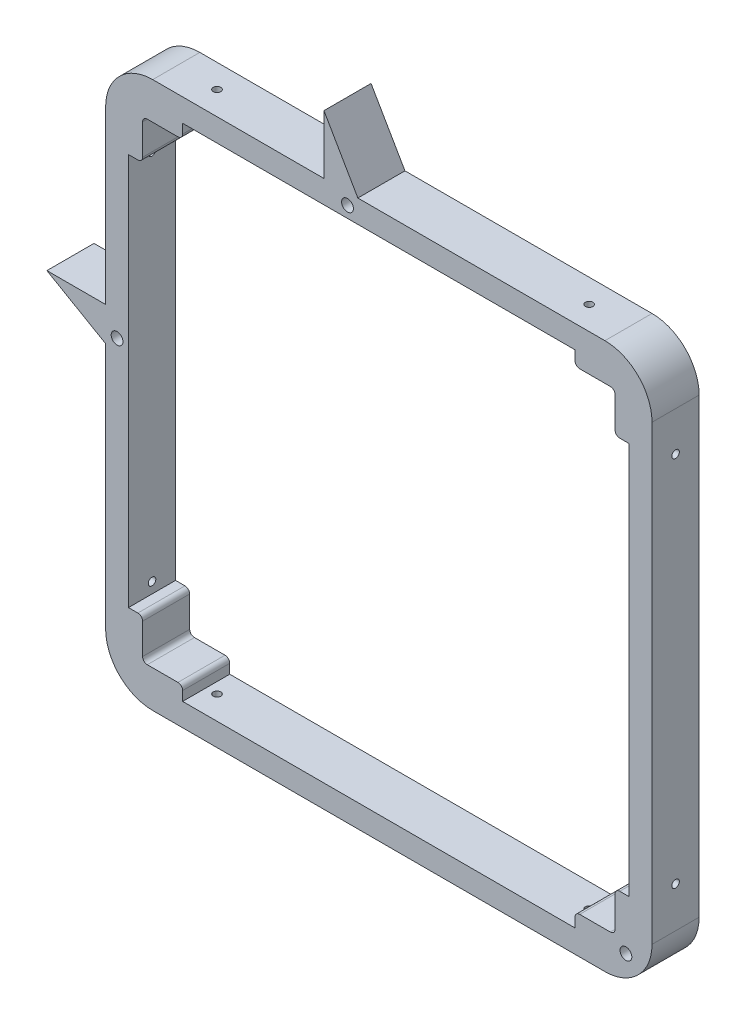
SolidWorks part; units mm, degrees
material "Nylon 101"
ref_plane "Front Plane" through (0, 0, 0) normal (0, 0, 1) x (1, 0, 0)
ref_plane "Top Plane" through (0, 0, 0) normal (0, 1, 0) x (1, 0, 0)
ref_plane "Right Plane" through (0, 0, 0) normal (1, 0, 0) x (0, 0, -1)
sketch "Sketch1" plane through (0, 0, 0) normal (0, 0, 1) x (1, 0, 0)
  line L13 (50.0019, -50.0019) -> (58, -58) construction
  line L14 (53, -41.5) -> (50.0019, -41.5)
  line L17 (41.5, -53) -> (41.5, -50.0019)
  line L18 (50.0019, -44.9586) -> (53, -44.9586)
  line L20 (53, -44.9586) -> (53, -53)
  line L23 (53, -53) -> (44.9586, -53)
  line L24 (44.9586, -53) -> (44.9586, -50.0019)
  line L25 (50.0019, -41.5) -> (50.0019, -50.0019)
  line L27 (50.0019, -50.0019) -> (41.5, -50.0019)
  line L35 (-41.5, 53) -> (41.5, 53)
  line L37 (50.0019, -50.0019) -> (50.0019, -41.5)
  line L38 (41.5, -50.0019) -> (50.0019, -50.0019)
  line L39 (53, -44.9586) -> (50.0019, -44.9586)
  line L40 (53, -53) -> (53, -44.9586)
  line L42 (44.9586, -53) -> (53, -53)
  line L43 (44.9586, -50.0019) -> (44.9586, -53)
  line L44 (53, -41.5) -> (50.0019, -41.5)
  line L45 (41.5, -53) -> (41.5, -50.0019)
  line L47 (53, -41.5) -> (53, 41.5)
  line L50 (41.5, -53) -> (-41.5, -53)
  line L52 (-41.5, -53) -> (-41.5, -50.0019)
  line L53 (-53, -41.5) -> (-50.0019, -41.5)
  line L54 (-44.96, -50.0019) -> (-44.96, -53)
  line L55 (-44.96, -53) -> (-53, -53)
  line L57 (-53, -53) -> (-53, -44.96)
  line L58 (-53, -44.96) -> (-50.0019, -44.96)
  line L59 (-41.5, -50.0019) -> (-50.0019, -50.0019)
  line L60 (-50.0019, -50.0019) -> (-50.0019, -41.5)
  line L61 (-53, -41.5) -> (-53, 41.5)
  line L63 (58, 58) -> (58, -58)
  line L65 (-50.0019, -50.0019) -> (-41.5, -50.0019)
  line L66 (-50.0019, -41.5) -> (-50.0019, -50.0019)
  line L67 (-44.96, -53) -> (-44.96, -50.0019)
  line L68 (-53, -53) -> (-44.96, -53)
  line L70 (-53, -44.96) -> (-53, -53)
  line L71 (-50.0019, -44.96) -> (-53, -44.96)
  line L72 (-41.5, -53) -> (-41.5, -50.0019)
  line L73 (-53, -41.5) -> (-50.0019, -41.5)
  line L75 (58, -58) -> (-58, -58)
  line L77 (-50.0019, -50.0019) -> (-58, -58) construction
  line L79 (-58, -58) -> (-58, 58)
  line L81 (-53, 41.5) -> (-50.0019, 41.5)
  line L82 (-41.5, 53) -> (-41.5, 50.0019)
  line L83 (-50.0019, 44.96) -> (-53, 44.96)
  line L84 (-53, 44.96) -> (-53, 53)
  line L86 (-53, 53) -> (-44.96, 53)
  line L87 (-44.96, 53) -> (-44.96, 50.0019)
  line L88 (-50.0019, 41.5) -> (-50.0019, 50.0019)
  line L89 (-50.0019, 50.0019) -> (-41.5, 50.0019)
  line L90 (-58, 58) -> (58, 58)
  line L94 (-50.0019, 50.0019) -> (-50.0019, 41.5)
  line L95 (-41.5, 50.0019) -> (-50.0019, 50.0019)
  line L96 (-53, 44.96) -> (-50.0019, 44.96)
  line L97 (-53, 53) -> (-53, 44.96)
  line L99 (-44.96, 53) -> (-53, 53)
  line L100 (-44.96, 50.0019) -> (-44.96, 53)
  line L101 (-53, 41.5) -> (-50.0019, 41.5)
  line L102 (-41.5, 53) -> (-41.5, 50.0019)
  line L106 (-50.0019, 50.0019) -> (-58, 58) construction
  line L110 (41.5, 53) -> (41.5, 50.0019)
  line L111 (53, 41.5) -> (50.0019, 41.5)
  line L112 (44.9586, 50.0019) -> (44.9586, 53)
  line L113 (44.9586, 53) -> (53, 53)
  line L115 (53, 53) -> (53, 44.96)
  line L116 (53, 44.96) -> (50.0019, 44.96)
  line L117 (41.5, 50.0019) -> (50.0019, 50.0019)
  line L118 (50.0019, 50.0019) -> (50.0019, 41.5)
  line L123 (50.0019, 50.0019) -> (41.5, 50.0019)
  line L124 (50.0019, 41.5) -> (50.0019, 50.0019)
  line L125 (44.9586, 53) -> (44.9586, 50.0019)
  line L126 (53, 53) -> (44.9586, 53)
  line L128 (53, 44.96) -> (53, 53)
  line L129 (50.0019, 44.96) -> (53, 44.96)
  line L130 (41.5, 53) -> (41.5, 50.0019)
  line L131 (53, 41.5) -> (50.0019, 41.5)
  line L135 (50.0019, 50.0019) -> (58, 58) construction
  point P2 (0, 58)
  point P4 (0, 53)
  point P6 (0, -53)
  point P7 (0, -58)
  point P10 (53, 0)
  point P11 (-53, 0)
  point P16 (-58, 0)
  point P17 (58, 0)
  dimension "D1" = 106
  dimension "D2" = 5
  dimension "D3" = 2.9981
extrude "base" add sketch "Sketch1" along normal mid plane 10 contours L20 L13 L14 L25 L18 | L13 L23 L24 L27 L17 | L13 L27 L24 L23 | L25 L13 L20 L18 | L117 L118 L116 L115 L113 L112 | L88 L89 L87 L86 L84 L83 | L59 L60 L58 L57 L55 L54 region at (51.5009, -45.0723, 0) region at (50.1156, 47.4809, 0) region at (-45.0737, -51.5009, 0) region at (-47.4809, 50.1156, 0) region at (56.3595, 0, 0)
ref_plane "Plane3" through (0, 0, 15) normal (0, 0, 1) x (1, 0, 0)
sketch "Sketch7" plane through (0, 0, 15) normal (0, 0, 1) x (1, 0, 0)
  line L0 (-41.65, 53.15) -> (41.65, 53.15)
  line L1 (41.65, 53.15) -> (41.65, 50.1519)
  line L2 (41.65, 50.1519) -> (50.1519, 50.1519)
  line L3 (50.1519, 50.1519) -> (50.1519, 41.65)
  line L4 (50.1519, 41.65) -> (53.15, 41.65)
  line L5 (53.15, 41.65) -> (53.15, -41.65)
  line L6 (53.15, -41.65) -> (50.1519, -41.65)
  line L7 (50.1519, -41.65) -> (50.1519, -50.1519)
  line L8 (50.1519, -50.1519) -> (41.65, -50.1519)
  line L9 (41.65, -50.1519) -> (41.65, -53.15)
  line L10 (41.65, -53.15) -> (-41.65, -53.15)
  line L11 (-41.65, -53.15) -> (-41.65, -50.1519)
  line L12 (-41.65, -50.1519) -> (-50.1519, -50.1519)
  line L13 (-50.1519, -50.1519) -> (-50.1519, -41.65)
  line L14 (-50.1519, -41.65) -> (-53.15, -41.65)
  line L15 (-53.15, -41.65) -> (-53.15, 41.65)
  line L16 (-53.15, 41.65) -> (-50.1519, 41.65)
  line L17 (-50.1519, 41.65) -> (-50.1519, 50.1519)
  line L18 (-50.1519, 50.1519) -> (-41.65, 50.1519)
  line L19 (-41.65, 50.1519) -> (-41.65, 53.15)
  line L21 (-41.5, 53) -> (41.5, 53) construction
  line L22 (-41.5, 53) -> (-41.5, 50.0019) construction
  line L23 (-50.0019, 50.0019) -> (-41.5, 50.0019) construction
  line L24 (-50.0019, 41.5) -> (-50.0019, 50.0019) construction
  line L25 (-53, 41.5) -> (-50.0019, 41.5) construction
  line L26 (-53, -41.5) -> (-53, 41.5) construction
  line L27 (-53, -41.5) -> (-50.0019, -41.5) construction
  line L28 (-50.0019, -50.0019) -> (-50.0019, -41.5) construction
  line L29 (-41.5, -50.0019) -> (-50.0019, -50.0019) construction
  line L30 (-41.5, -53) -> (-41.5, -50.0019) construction
  line L31 (41.5, -53) -> (-41.5, -53) construction
  line L32 (41.5, -53) -> (41.5, -50.0019) construction
  line L33 (50.0019, -41.5) -> (50.0019, -50.0019) construction
  line L34 (53, -41.5) -> (53, 41.5) construction
  line L35 (50.0019, 50.0019) -> (50.0019, 41.5) construction
  line L36 (53, 41.5) -> (50.0019, 41.5) construction
  line L37 (41.5, 50.0019) -> (50.0019, 50.0019) construction
  dimension "D1" = 0.15
  dimension "D2" = 0.15
  dimension "D3" = 0.15
  dimension "D4" = 0.15
  dimension "D5" = 0.15
  dimension "D6" = 0.15
  dimension "D7" = 0.15
  dimension "D8" = 0.15
  dimension "D9" = 0.15
  dimension "D10" = 0.15
  dimension "D11" = 0.15
  dimension "D12" = 0.15
  dimension "D13" = 0.15
  dimension "D14" = 0.15
  dimension "D15" = 0.15
  dimension "D16" = 0.15
  dimension "D17" = 0.15
ref_plane "arm plane" through (0, 0, 0) normal (0.7071, 0.7071, 0) x (0.7071, -0.7071, 0)
sketch "Sketch2" plane through (0, 0, 0) normal (0.7071, 0.7071, 0) x (0.7071, -0.7071, 0)
  line L4 (70.9255, 5) -> (82.0244, 5)
  line L8 (82.0244, 5) -> (82.0244, 44)
  line L9 (82.0244, 44) -> (32.0244, 44)
  line L12 (32.0244, 44) -> (32.0244, 33)
  line L13 (32.0244, 33) -> (70.9255, 33)
  line L14 (70.9255, 33) -> (70.9255, 5)
  dimension "D1" = 50
  dimension "D2" = 11
  dimension "D4" = 28
extrude "arm" add sketch "Sketch2" along normal mid plane 10
ref_plane "shim supports plane" through (0, 0, -5) normal (0, 0, -1) x (-1, 0, 0)
sketch "Sketch3" plane through (0, 0, 0) normal (0, 0, 1) x (1, 0, 0)
  line L1 (61.5355, -54.4645) -> (54.4645, -61.5355) construction
  line L6 (58, 58) -> (58, -50.9289) construction
  line L7 (50.9289, -58) -> (-58, -58) construction
  line L8 (19.1091, -26.1802) -> (46.6163, -53.6874) construction
  line L9 (58, -50.9289) -> (61.5355, -54.4645) construction
  line L10 (54.818, -61.8891) -> (61.8891, -54.818)
  line L11 (61.8891, -54.818) -> (58, -50.9289)
  line L12 (58, -50.9289) -> (58, -58)
  line L13 (58, -58) -> (50.9289, -58)
  line L14 (50.9289, -58) -> (54.818, -61.8891)
  dimension "D1" = 0.5
extrude "Cut-Extrude1" cut sketch "Sketch3" against normal through all
ref_plane "Plane2" through (0, 0, -5) normal (0, 0, -1) x (-1, 0, 0)
sketch "Sketch5" plane through (0, 0, -5) normal (0, 0, -1) x (-1, 0, 0)
  line L0 (-46.6163, -53.6874) -> (-43.0808, -50.1519)
  line L7 (-50.1519, -43.0808) -> (-53.6874, -46.6163)
  line L8 (-53.6874, -46.6163) -> (-53.6874, -53.6874)
  line L9 (-50.0019, -50.0019) -> (-58, -58) construction
  line L10 (-53.6874, -53.6874) -> (-46.6163, -53.6874)
  line L12 (-53.6874, -46.6163) -> (-58, -50.9289) construction
  line L14 (-50.1519, -41.65) -> (-50.1519, -50.1519) construction
  line L15 (-50.1519, -50.1519) -> (-41.65, -50.1519) construction
  line L16 (-50.1519, -43.0808) -> (-50.1519, -50.1519)
  line L17 (-50.1519, -50.1519) -> (-43.0808, -50.1519)
  dimension "D1" = 5
  dimension "D2" = 10
extrude "Boss-Extrude4" add sketch "Sketch5" along normal up to surface (28 mm away) contours L8 L10 L0 L7 | L7 L8 L10 L0 L17 L16 region at (50.1519, -53.5374, -5) up to face at (36.3983, -36.3983, -33)
extrude "clearance" cut sketch "Sketch7" against normal up to surface (20 mm away) up to face at (0, 0, -5)
sketch "Sketch10" plane through (0, 0, 0) normal (0, 1, 0) x (1, 0, 0)
  line L0 (41.65, 5) -> (41.65, -5) construction
  circle A0 centre (39.65, 0) radius 0.8
  circle A1 centre (-39.35, 0) radius 0.8
  point P5 (41.65, 0)
  dimension "D1" = 1.6
  dimension "D2" = 2
  dimension "D3" = 79
hole_wizard "M2x0.4 Tapped Hole1" positions "Sketch11" profile "Sketch12" tap size "M2x0.4" standard "ANSI Metric" end condition through all
sketch "Sketch11" plane through (0, 0, 0) normal (0, 1, 0) x (1, 0, 0)
  point P0 (-39.35, 0)
  point P2 (39.65, 0)
sketch "Sketch12" plane through (-39.35, 0, 0) normal (1, 0, 0) x (0, 0, -1)
  line L0 (0, 0) -> (0, 58)
  line L1 (0, 58) -> (0.8, 58)
  line L2 (0.8, 58) -> (0.8, 0)
  line L5 (0.8, 0) -> (0, 0)
  line L11 (0, -6.35) -> (0, 107.95) construction
  dimension "Thru Tap Drill Dia." = 1.6
  dimension "Thru Tap Drill Depth" = 58
cosmetic thread "Hole Thread1" parameters "D2"=2
cosmetic thread "Hole Thread2" parameters "D2"=2
mirror "Mirror1" about plane through (0, 0, 0) normal (0, 1, 0) of "M2x0.4 Tapped Hole1"
cosmetic thread "Hole Thread3" parameters "D2"=2
cosmetic thread "Hole Thread4" parameters "D2"=2
sketch "Sketch13" plane through (0, 0, 0) normal (1, 0, 0) x (0, 0, -1)
  line L2 (5, 41.65) -> (-5, 41.65) construction
  circle A0 centre (0, 39.65) radius 0.8
  circle A1 centre (0, -39.35) radius 0.8
  dimension "D1" = 1.6
  dimension "D3" = 79
  dimension "D2" = 2
hole_wizard "M2x0.4 Tapped Hole2" positions "Sketch14" profile "Sketch15" tap size "M2x0.4" standard "ANSI Metric" end condition through all
sketch "Sketch14" plane through (0, 0, 0) normal (1, 0, 0) x (0, 0, -1)
  point P0 (0, 39.65)
  point P3 (0, -39.35)
sketch "Sketch15" plane through (0, 39.65, 0) normal (0, 1, 0) x (0, 0, 1)
  line L0 (0, 0) -> (0, 58)
  line L1 (0, 58) -> (0.8, 58)
  line L2 (0.8, 58) -> (0.8, 0)
  line L5 (0.8, 0) -> (0, 0)
  line L11 (0, -6.35) -> (0, 107.95) construction
  dimension "Thru Tap Drill Dia." = 1.6
  dimension "Thru Tap Drill Depth" = 58
cosmetic thread "Hole Thread5" parameters "D2"=2
cosmetic thread "Hole Thread6" parameters "D2"=2
mirror "Mirror2" about plane through (0, 0, 0) normal (1, 0, 0) of "M2x0.4 Tapped Hole2"
cosmetic thread "Hole Thread7" parameters "D2"=2
cosmetic thread "Hole Thread8" parameters "D2"=2
sketch "Sketch16" plane through (0, 0, -5) normal (0, 0, -1) x (-1, 0, 0)
  line L0 (53.15, 11.65) -> (70.4705, 11.65)
  line L6 (53.15, -41.65) -> (53.15, 41.65) construction
  line L10 (-58, -58) -> (58, 58) construction
  line L18 (70.4705, 11.65) -> (53.15, 1.65)
  line L19 (53.15, 1.65) -> (53.15, 11.65)
  dimension "D1" = 20
  dimension "D2" = 10
  dimension "D3" = 30
extrude "extender" add sketch "Sketch16" along normal blind 29 contours L19 L18 region at (-58.9235, 8.3167, -5)
ref_plane "Plane5" through (0, 0, -34) normal (0, 0, -1) x (-1, 0, 0)
sketch "Sketch17" plane through (0, 0, -34) normal (0, 0, -1) x (-1, 0, 0)
  line L2 (106.183, 64.683) -> (114.8433, 56.0228)
  line L4 (53.15, 1.65) -> (53.15, 11.65)
  line L5 (53.15, 11.65) -> (106.183, 64.683)
  line L9 (-50.9289, -58) -> (-19.1091, -26.1802) construction
  line L14 (114.8433, 56.0228) -> (70.4705, 11.65)
  line L15 (70.4705, 11.65) -> (53.15, 1.65)
  dimension "D2" = 75
extrude "angled horizontal" add sketch "Sketch17" along normal blind 10
sketch "Sketch21" plane through (0, 0, 0) normal (0, 0, 1) x (1, 0, 0)
  line L0 (-53.15, 1.65) -> (-53.15, 11.65)
  line L1 (-70.4705, 11.65) -> (-53.15, 11.65)
  line L2 (-70.4705, 11.65) -> (-53.15, 1.65)
  line L6 (-70.4705, 11.65) -> (-58, 4.4501) construction
  line L8 (3.8891, -3.8891) -> (-3.8891, 3.8891) construction
  line L9 (-11.65, 70.4705) -> (-1.65, 53.15)
  line L10 (-11.65, 70.4705) -> (-11.65, 53.15)
  line L11 (-1.65, 53.15) -> (-11.65, 53.15)
  line L12 (-53.15, 38.85) -> (-53.15, 40.45) construction
  line L14 (-53.15, 11.65) -> (-53.15, 1.65) construction
extrude "Arm Holder" add sketch "Sketch21" along normal up to surface (5 mm away) and the other way up to surface (5 mm away) up to face at (0, 0, 5) other way up to face at (-62.1568, 9.25, -5)
fillet "Fillet1" radius 1 12 edges at (50.1519, -41.65, 0) (41.65, -50.1519, 0) (-50.1519, -41.65, 0) (-41.65, -50.1519, 0) (-50.1519, 41.65, 0) (-41.65, 50.1519, 0) (41.65, 50.1519, 0) (50.1519, 41.65, 0) (50.1519, 50.1519, 0) (50.1519, -50.1519, -14) (-50.1519, -50.1519, 0) (-50.1519, 50.1519, 0)
fillet "Fillet2" radius 10 4 edges at (58, -58, -19.5) (58, 58, 0) (-58, 58, 0) (-58, -58, 0)
hole_wizard "M3x0.5 Tapped Hole2" positions "Sketch28" profile "Sketch29" tap size "M3x0.5" standard "ANSI Metric" end condition through all
sketch "Sketch28" plane through (0, 0, -44) normal (0, 0, -1) x (-1, 0, 0)
  line L1 (-57.6593, -50.5882) -> (-26.1802, -19.1091) construction
  arc A0 (-57.6593, -50.5882) -> (-50.5882, -57.6593) centre (-48, -48) ccw construction
  point P0 (-52.4654, -52.4654)
  point P11 (-55.0711, -55.0711)
  dimension "D1" = 5
  dimension "D2" = 3.685
sketch "Sketch29" plane through (52.4654, -52.4654, -44) normal (1, 0, 0) x (0, 1, 0)
  line L0 (0, 0) -> (0, 49)
  line L1 (0, 49) -> (1.25, 49)
  line L2 (1.25, 49) -> (1.25, 0)
  line L5 (1.25, 0) -> (0, 0)
  line L11 (0, -6.35) -> (0, 107.95) construction
  dimension "Thru Tap Drill Dia." = 2.5
  dimension "Thru Tap Drill Depth" = 49
cosmetic thread "Hole Thread13" parameters "D2"=3
hole_wizard "M3x0.5 Tapped Hole3" positions "Sketch36" profile "Sketch38" tap size "M3x0.5" standard "ANSI Metric"
sketch "Sketch36" plane through (0, 0, 5) normal (0, 0, 1) x (1, 0, 0)
  line L0 (-53.15, 41.65) -> (-53.15, -41.65) construction
  line L1 (-53.15, 11.65) -> (-53.15, 1.65) construction
  point P0 (-55.575, 6.65)
  point P9 (-53.15, 6.65)
  dimension "D1" = 2.425
sketch "Sketch38" plane through (-55.575, 6.65, 5) normal (1, 0, 0) x (0, -1, 0)
  line L0 (0, 0) -> (0, 30.5611)
  line L1 (0, 30.5611) -> (1.25, 29.81)
  line L2 (1.25, 29.81) -> (1.25, 0)
  line L5 (1.25, 0) -> (0, 0)
  line L10 (0, 30.5611) -> (-1.25, 29.81) construction
  line L11 (0, -6.35) -> (0, 107.95) construction
  dimension "Tap Drill Dia." = 2.5
  dimension "Tap Drill Depth" = 29.81
  dimension "Drill Angle" = 118
cosmetic thread "Hole Thread14" parameters "D1"=28.31, "D2"=3
mirror "U part of Outside arm" about plane through (0, 0, 0) normal (0.7071, 0.7071, 0) of "M3x0.5 Tapped Hole3", "angled horizontal", "extender"
cosmetic thread "Hole Thread15" parameters "D1"=28.31, "D2"=3
sketch "Sketch39" plane through (0, 0, 0) normal (0.7071, 0.7071, 0) x (0.7071, -0.7071, 0)
  line L0 (-58.068, 44) -> (-120.8205, 44) construction
  line L1 (-120.8205, 44) -> (-116.8205, 44)
  line L2 (-120.8205, 44) -> (-120.8205, 34)
  line L3 (-120.8205, 34) -> (-116.8205, 34)
  line L4 (-116.8205, 44) -> (-116.8205, 34)
  line L5 (-120.8205, 44) -> (-116.8205, 34) construction
  line L6 (-120.8205, 34) -> (-116.8205, 44) construction
  line L7 (-120.8205, 44) -> (-120.8205, 34) construction
  point P0 (-118.8205, 39)
  dimension "D1" = 4
extrude "Boss-Extrude18" add sketch "Sketch39" along normal up to next and the other way up to next
ref_plane "Plane12" through (0, 0, 0) normal (0.7071, -0.7071, 0) x (0, 0, -1)
ref_plane "Plane13" through (27.061, -27.061, 0) normal (0.7071, -0.7071, 0) x (0, 0, -1)
sketch "Sketch34" plane through (27.061, -27.061, 0) normal (0.7071, -0.7071, 0) x (0, 0, -1)
  line L0 (44, 5) -> (33, 5)
  line L1 (33, 5) -> (9, 36.8955)
  line L2 (9, 36.8955) -> (20, 36.8955)
  line L3 (20, 36.8955) -> (44, 5)
  line L4 (5, 5) -> (44, 5) construction
  line L5 (5, 67.0337) -> (5, 8.1317) construction
  line L6 (-5, 36.8955) -> (5, 36.8955) construction
  dimension "D1" = 4
extrude "Shim support arm" add sketch "Sketch34" along normal blind 6.85
sketch "Sketch35" plane through (0, 0, -5) normal (0, 0, -1) x (-1, 0, 0)
  line L1 (-57.9937, -5.8156) -> (-35.4402, -28.3691) construction
  line L8 (-53.15, -0.972) -> (-57.9937, -5.8156)
  line L9 (-57.9937, -5.8156) -> (-53.15, -10.6593)
  line L10 (-53.15, 41.65) -> (-53.15, -41.65) construction
  line L11 (-53.15, -10.6593) -> (-53.15, -0.972)
  line L14 (-57.9937, -5.8156) -> (-53.15, -0.972) construction
extrude "Boss-Extrude17" add sketch "Sketch35" along normal up to surface (4 mm away) up to face at (44.2951, -14.6705, -21)
mirror "Mirror4" about plane through (0, 0, 0) normal (0.7071, 0.7071, 0) of "Boss-Extrude17", "Shim support arm"
fillet "Fillet4" radius 2 8 edges at (55.5718, -3.3938, -20) (53.15, -5.8156, -11.5772) (30.5965, -23.5254, -38.5) (35.4402, -28.3691, -38.5) (5.8156, -53.15, -11.5772) (3.3938, -55.5718, -20) (28.3691, -35.4402, -38.5) (23.5254, -30.5965, -38.5)
split "Split1" bodies to split 139 resulting bodies 142 split by face at (-14.9453, -45.9956, -5)
